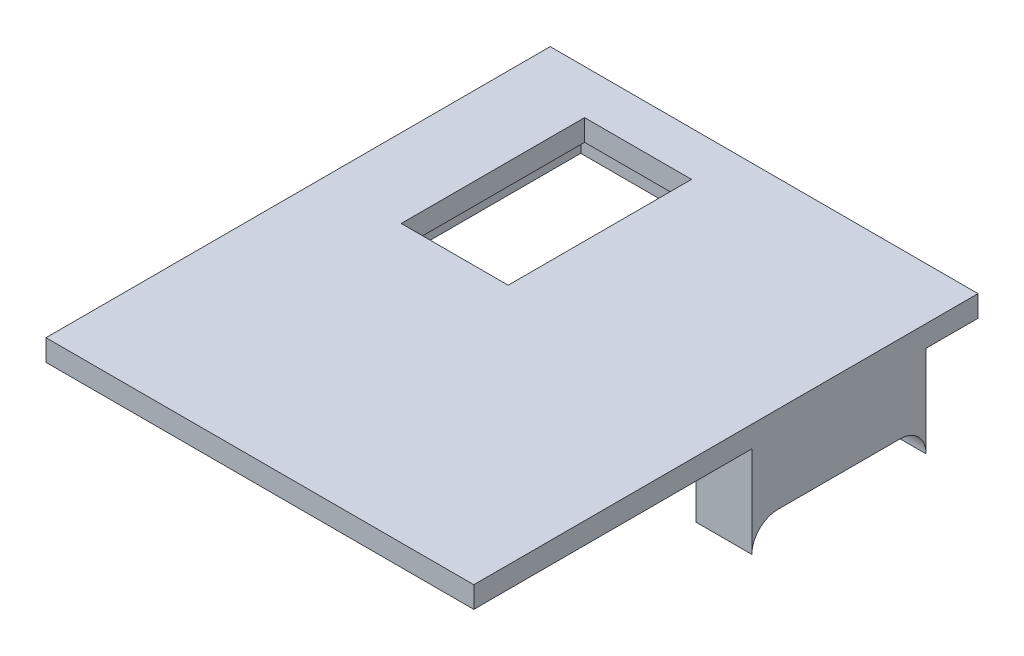
SolidWorks part; units mm, degrees
ref_plane "Płaszczyzna przednia" through (0, 0, 0) normal (0, 0, 1) x (1, 0, 0)
ref_plane "Płaszczyzna górna" through (0, 0, 0) normal (0, 1, 0) x (1, 0, 0)
ref_plane "Płaszczyzna prawa" through (0, 0, 0) normal (1, 0, 0) x (0, 0, -1)
sketch "Szkic1" plane through (0, 0, 0) normal (0, 1, 0) x (1, 0, 0)
  line L1 (-14, -16.5) -> (14, -16.5)
  line L2 (-14, -16.5) -> (-14, 16.5)
  line L3 (-14, 16.5) -> (14, 16.5)
  line L4 (14, -16.5) -> (14, 16.5)
  line L5 (-14, -16.5) -> (14, 16.5) construction
  line L6 (-14, 16.5) -> (14, -16.5) construction
  point P0 (0, 0)
  dimension "D1" = 28
  dimension "D2" = 33
extrude "Dodanie-wyciągnięcie1" add sketch "Szkic1" along normal blind 1.4
sketch "Szkic2" plane through (0, 0, 0) normal (0, -1, 0) x (1, 0, 0)
  line L5 (-9.35, 13.85) -> (9.35, 13.85)
  line L6 (-10.35, -14.85) -> (10.35, -14.85)
  line L10 (-10.35, -14.85) -> (-10.35, 14.85)
  line L11 (-10.35, 14.85) -> (10.35, 14.85)
  line L12 (10.35, -14.85) -> (10.35, 14.85)
  line L13 (-10.35, -14.85) -> (10.35, 14.85) construction
  line L14 (-10.35, 14.85) -> (10.35, -14.85) construction
  line L15 (9.35, 13.85) -> (9.35, -13.85)
  line L16 (9.35, -13.85) -> (-9.35, -13.85)
  line L17 (-9.35, -13.85) -> (-9.35, 13.85)
  line L18 (-14, 16.5) -> (14, 16.5) construction
  line L20 (14, 16.5) -> (14, -16.5) construction
  point P0 (0, 0)
  dimension "D2" = 1.65
  dimension "D3" = 1
  dimension "D4" = 1
  dimension "D5" = 1
  dimension "D6" = 1
  dimension "D7" = 3.65
extrude "Dodanie-wyciągnięcie2" add sketch "Szkic2" along normal blind 1
sketch "Szkic3" plane through (0, 0, 0) normal (0, -1, 0) x (1, 0, 0)
  line L0 (-9.35, -13.85) -> (-5.35, -13.85) construction
  line L1 (-5.35, -13.85) -> (-5.35, -7.6) construction
  line L2 (-9.35, -13.85) -> (9.35, -13.85) construction
  line L3 (-1.85, -13.6) -> (-8.85, -13.6)
  line L4 (-1.85, -13.6) -> (-1.85, -1.6)
  line L5 (-1.85, -1.6) -> (-8.85, -1.6)
  line L6 (-8.85, -13.6) -> (-8.85, -1.6)
  line L7 (-1.85, -13.6) -> (-8.85, -1.6) construction
  line L8 (-1.85, -1.6) -> (-8.85, -13.6) construction
  line L9 (-9.35, 13.85) -> (-9.35, -13.85) construction
  point P7 (-6.1, -8.35)
  dimension "D1" = 4
  dimension "D2" = 6.25
  dimension "D3" = 12
  dimension "D4" = 7
extrude "Wytnij-wyciągnięcie1" cut sketch "Szkic3" against normal through all
sketch "Szkic4" plane through (10.35, 0, 0) normal (1, 0, 0) x (0, 0, -1)
  line L0 (16.5, 0) -> (13.1, 0) construction
  line L1 (16.5, 1.4) -> (16.5, 0) construction
  line L2 (-16.5, 0) -> (16.5, 0) construction
  line L3 (13.1, 0) -> (13.1, -5.9847)
  line L4 (13.1, 0) -> (1.7, 0)
  line L5 (1.7, 0) -> (1.7, -5.9847)
  line L6 (7.4, 0) -> (7.4, -4.2847) construction
  line L7 (3.4, -4.2847) -> (11.4, -4.2847)
  line L8 (11.4, -4.2847) -> (11.4, -5.9847) construction
  arc A0 (11.4, -4.2847) -> (13.1, -5.9847) centre (11.4, -5.9847) cw
  arc A1 (3.4, -4.2847) -> (1.7, -5.9847) centre (3.4, -5.9847) ccw
  point P9 (0, 0)
  point P14 (7.4, -4.2847)
  point P16 (13.1, -4)
  point P17 (13.1, -4.3391)
  point P19 (1.729, -4.2564)
  point P20 (16.5, 0)
  dimension "D1" = 3.4
  dimension "D2" = 11.4
  dimension "D4" = 8
  dimension "D5" = 1.7
extrude "Dodanie-wyciągnięcie3" add sketch "Szkic4" along normal up to surface (3.65 mm away) up to face at (14, 0.7, 0)
